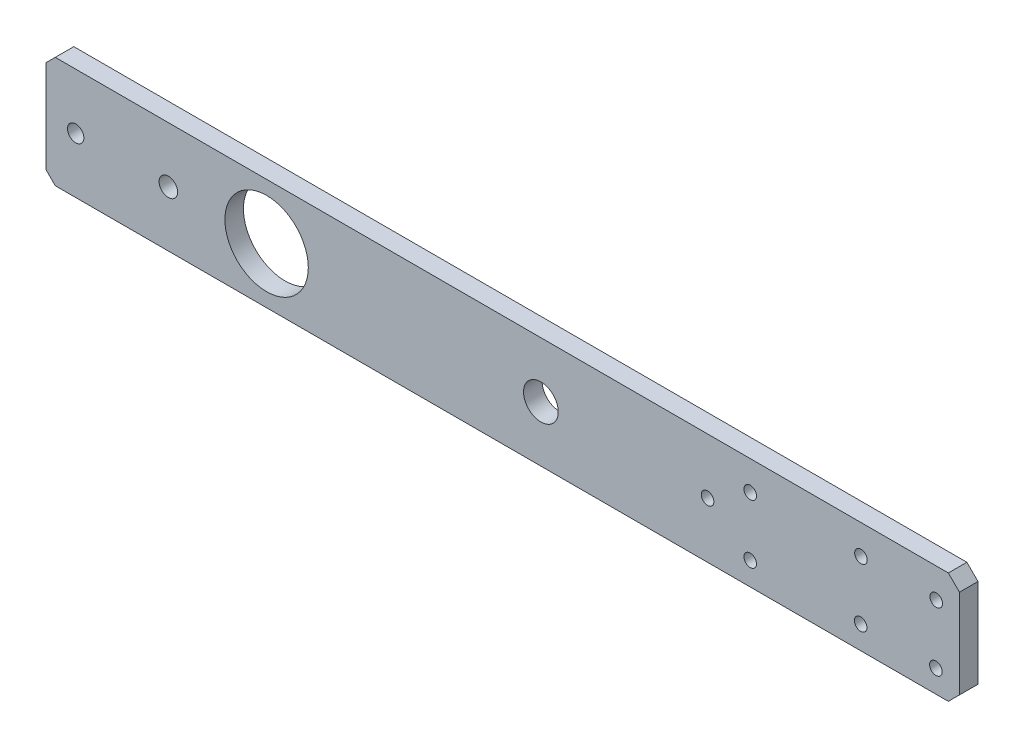
SolidWorks part; units mm, degrees
material "6061-T6 (SS)"
ref_plane "Front Plane" through (0, 0, 0) normal (0, 0, 1) x (1, 0, 0)
ref_plane "Top Plane" through (0, 0, 0) normal (0, 1, 0) x (1, 0, 0)
ref_plane "Right Plane" through (0, 0, 0) normal (1, 0, 0) x (0, 0, -1)
sketch "Sketch1" plane through (0, 0, 0) normal (0, 0, 1) x (1, 0, 0)
  line L0 (0, 19.05) -> (-28.575, 19.05)
  line L1 (0, -19.05) -> (247.2819, -19.05)
  line L2 (0, -19.05) -> (0, 19.05) construction
  line L3 (0, 19.05) -> (254, 19.05)
  line L5 (-28.575, 19.05) -> (-28.575, -19.05)
  line L6 (-28.575, -19.05) -> (0, -19.05)
  line L8 (254, 19.05) -> (247.2819, -19.05)
  circle A1 centre (0, 0) radius 14.2875
  dimension "D3" = 28.575
  dimension "D1" = 38.1
  dimension "D2" = 254
  dimension "D4" = 80
extrude "Boss-Extrude1" add sketch "Sketch1" along normal mid plane 6.35
hole_wizard "#6 Clearance Hole3" positions "Sketch8" profile "Sketch7" hole size "#6" standard "ANSI Inch" end condition through all
sketch "Sketch8" plane through (0, 0, 3.175) normal (0, 0, 1) x (1, 0, 0)
  line L9 (159.3222, 8.9914) -> (175.5726, 8.9914) construction
  line L12 (159.3222, -11.1439) -> (172.0222, -11.1439) construction
  line L13 (159.3222, 19.05) -> (159.3222, -19.05) construction
  line L26 (254, 19.05) -> (-28.575, 19.05) construction
  line L28 (-28.575, -19.05) -> (247.2819, -19.05) construction
  line L29 (159.3222, 0) -> (151.0672, 0) construction
  line L30 (165.6722, 8.9914) -> (165.6722, -11.1439) construction
  line L32 (177.3462, 19.05) -> (170.6012, -19.2024) construction
  point P0 (229.3887, 8.9238)
  point P3 (229.2824, -11.3468)
  point P6 (203.5032, -11.1439)
  point P9 (203.6088, 8.9914)
  point P12 (165.6722, 8.9914)
  point P15 (165.6722, -11.1439)
  point P18 (151.0672, 0)
  dimension "D1" = 6.35
  dimension "D2" = 8.255
sketch "Sketch7" plane through (229.3887, 8.9238, 3.175) normal (1, 0, 0) x (0, -1, 0)
  line L0 (0, 0) -> (0, 6.35)
  line L1 (0, 6.35) -> (2.1526, 6.35)
  line L2 (2.1526, 6.35) -> (2.1526, 0)
  line L5 (2.1526, 0) -> (0, 0)
  line L11 (0, -6.35) -> (0, 107.95) construction
  dimension "Thru Hole Dia." = 4.3053
  dimension "Thru Hole Depth" = 6.35
sketch "Sketch9" plane through (0, 0, 3.175) normal (0, 0, 1) x (1, 0, 0)
  line L0 (254, 19.05) -> (247.2819, -19.05)
  line L1 (254, 19.05) -> (237.3521, 19.05)
  line L2 (254, 19.05) -> (-28.575, 19.05) construction
  line L3 (237.3521, 19.05) -> (237.3521, -19.05)
  line L4 (-28.575, -19.05) -> (247.2819, -19.05) construction
  line L5 (237.3521, -19.05) -> (247.2819, -19.05)
  line L6 (243.8073, 17.5595) -> (237.0893, -20.5405) construction
extrude "Cut-Extrude1" cut sketch "Sketch9" against normal through all
chamfer "Chamfer1" distance 3.81 angle 45 4 edges at (-28.575, -19.05, 0) (-28.575, 19.05, 0) (237.3521, 19.05, 0) (237.3521, -19.05, 0)
sketch "Sketch10" plane through (0, 0, 3.175) normal (0, 0, 1) x (1, 0, 0)
  line L0 (-24.765, -19.05) -> (233.5421, -19.05) construction
  line L1 (-24.765, -19.05) -> (-75.565, -19.05)
  line L2 (-24.765, -19.05) -> (-24.765, 19.05)
  line L3 (-24.765, 19.05) -> (-75.565, 19.05)
  line L4 (-75.565, -19.05) -> (-75.565, 19.05)
  dimension "D1" = 50.8
extrude "Boss-Extrude2" add sketch "Sketch10" against normal through all
chamfer "Chamfer2" distance 3.175 angle 45 2 edges at (-75.565, -19.05, 0) (-75.565, 19.05, 0)
hole_wizard "CSK for #10 Flat Head Machine Screw (100)1" positions "Sketch11" profile "Sketch12" countersink size "#10" standard "ANSI Inch" end condition through all
sketch "Sketch11" plane through (0, 0, 3.175) normal (0, 0, 1) x (1, 0, 0)
  line L0 (0, 0) -> (-75.565, 0) construction
  line L1 (-75.565, 15.875) -> (-75.565, -15.875) construction
  point P0 (-65.405, 0)
  dimension "D1" = 10.16
sketch "Sketch12" plane through (-65.405, 0, 3.175) normal (1, 0, 0) x (0, -1, 0)
  line L0 (0, 0) -> (0, 6.35)
  line L1 (0, 6.35) -> (2.8067, 6.35)
  line L2 (2.8067, 6.35) -> (2.8067, 1.7477)
  line L3 (2.8067, 1.7477) -> (4.8895, 0)
  line L5 (4.8895, 0) -> (0, 0)
  line L6 (-2.8067, 1.7477) -> (-4.8895, 0) construction
  line L11 (0, -6.35) -> (0, 107.95) construction
  dimension "Thru Hole Dia." = 5.6134
  dimension "Thru Hole Depth" = 6.35
  dimension "Near C'Sink Dia." = 9.779
  dimension "Near C'Sink Angle" = 100
hole_wizard "1/4 (0.25) Diameter Hole1" positions "Sketch13" profile "Sketch14" hole size "1/4" standard "ANSI Inch" end condition through all
sketch "Sketch13" plane through (0, 0, 3.175) normal (0, 0, 1) x (1, 0, 0)
  line L0 (-75.565, 0) -> (-33.655, 0) construction
  line L1 (-75.565, 15.875) -> (-75.565, -15.875) construction
  circle A0 centre (-65.405, 0) radius 4.8895 construction
  point P0 (-33.655, 0)
  dimension "D1" = 31.75
sketch "Sketch14" plane through (-33.655, 0, 3.175) normal (1, 0, 0) x (0, -1, 0)
  line L0 (0, 0) -> (0, 6.35)
  line L1 (0, 6.35) -> (3.175, 6.35)
  line L2 (3.175, 6.35) -> (3.175, 0)
  line L5 (3.175, 0) -> (0, 0)
  line L11 (0, -6.35) -> (0, 107.95) construction
  dimension "Thru Hole Dia." = 6.35
  dimension "Thru Hole Depth" = 6.35
hole_wizard "CSK for #6 Flat Head Machine Screw (100)1" positions "Sketch15" profile "Sketch16" countersink size "#6" standard "ANSI Inch" end condition through all
sketch "Sketch15" plane through (0, 0, -3.175) normal (0, 0, -1) x (-1, 0, 0)
  point P0 (-151.0672, 0)
  point P3 (-165.6722, -11.1439)
  point P6 (-165.6722, 8.9914)
sketch "Sketch16" plane through (151.0672, 0, -3.175) normal (1, 0, 0) x (0, 1, 0)
  line L0 (0, 0) -> (0, 6.35)
  line L1 (0, 6.35) -> (2.1526, 6.35)
  line L2 (2.1526, 6.35) -> (2.1526, 1.1669)
  line L3 (2.1526, 1.1669) -> (3.5433, 0)
  line L5 (3.5433, 0) -> (0, 0)
  line L6 (-2.1526, 1.1669) -> (-3.5433, 0) construction
  line L11 (0, -6.35) -> (0, 107.95) construction
  dimension "Thru Hole Dia." = 4.3053
  dimension "Thru Hole Depth" = 6.35
  dimension "Near C'Sink Dia." = 7.0866
  dimension "Near C'Sink Angle" = 100
hole_wizard "15/32 (0.46875) Diameter Hole1" positions "Sketch17" profile "Sketch18" hole size "15/32" standard "ANSI Inch" end condition through all
sketch "Sketch17" plane through (0, 0, -3.175) normal (0, 0, -1) x (-1, 0, 0)
  line L0 (75.565, 15.875) -> (75.565, -15.875) construction
  point P0 (-93.9672, 0)
  dimension "D1" = 169.5322
sketch "Sketch18" plane through (93.9672, 0, -3.175) normal (1, 0, 0) x (0, 1, 0)
  line L0 (0, 0) -> (0, 6.35)
  line L1 (0, 6.35) -> (5.9531, 6.35)
  line L2 (5.9531, 6.35) -> (5.9531, 0)
  line L5 (5.9531, 0) -> (0, 0)
  line L11 (0, -6.35) -> (0, 107.95) construction
  dimension "Thru Hole Dia." = 11.9062
  dimension "Thru Hole Depth" = 6.35
other "DeleteFace1" face at (163.5195, -11.1439, -2.0081) face at (148.9145, 0, -2.0081) face at (163.5195, 8.9914, -2.0081) face at (-62.5983, 0, 1.4273) and patch yes
